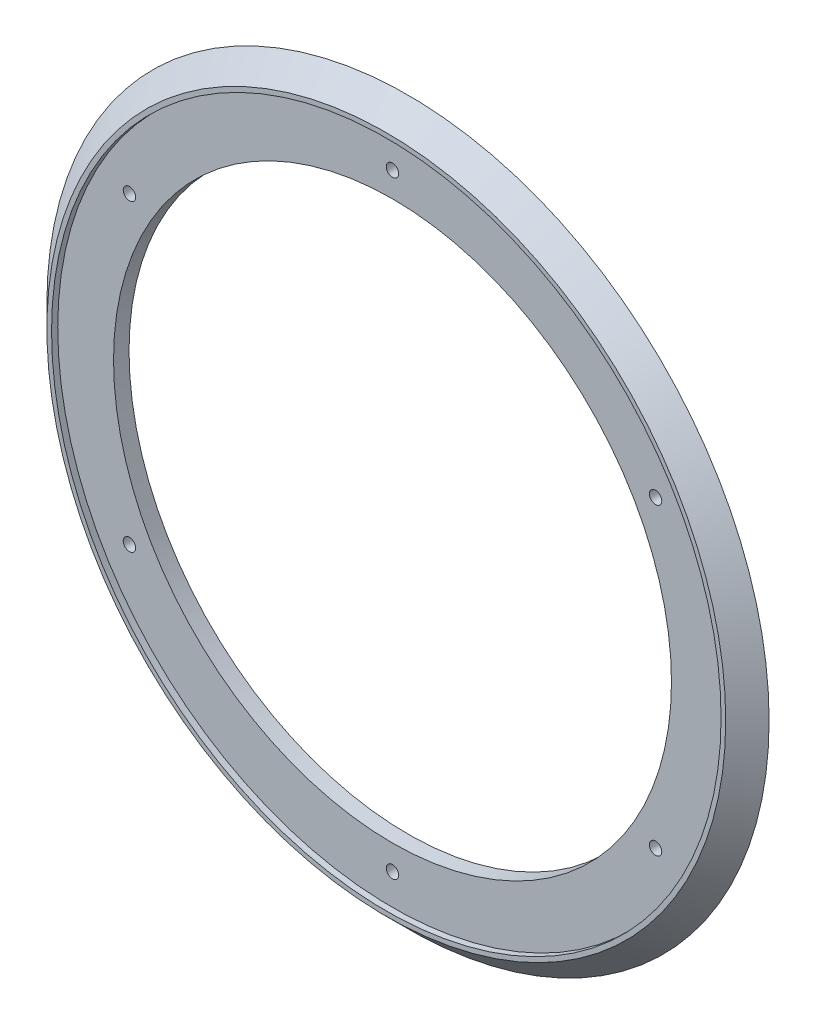
SolidWorks part; units mm, degrees
material "Gray Cast Iron (SN)"
ref_plane "Front Plane" through (0, 0, 0) normal (0, 0, 1) x (1, 0, 0)
ref_plane "Top Plane" through (0, 0, 0) normal (0, 1, 0) x (1, 0, 0)
ref_plane "Right Plane" through (0, 0, 0) normal (1, 0, 0) x (0, 0, -1)
sketch "Sketch1" plane through (0, 0, 0) normal (0, 0, 1) x (1, 0, 0)
  circle A0 centre (0, 0) radius 119.5
  dimension "D1" = 239
extrude "Boss-Extrude1" add sketch "Sketch1" along normal blind 7
chamfer "Chamfer2" distance 10 angle 45 1 edges at (119.5, 0, 7)
sketch "Sketch3" plane through (0, 0, 7) normal (0, 0, 1) x (1, 0, 0)
  circle A0 centre (0, 0) radius 108
  dimension "D1" = 216
extrude "Cut-Extrude1" cut sketch "Sketch3" against normal blind 2
sketch "Sketch4" plane through (0, 0, 0) normal (0, 0, -1) x (-1, 0, 0)
  circle A0 centre (0, 0) radius 90
  circle A1 centre (0, 0) radius 98 construction
  circle A2 centre (0, 98) radius 2
  circle A3 centre (84.8705, 49) radius 2
  circle A4 centre (84.8705, -49) radius 2
  circle A5 centre (0, -98) radius 2
  circle A6 centre (-84.8705, -49) radius 2
  circle A7 centre (-84.8705, 49) radius 2
  point P18 (0, 0)
  dimension "D1" = 180
  dimension "D2" = 196
  dimension "D3" = 4
  dimension "D4" = 6
extrude "Cut-Extrude2" cut sketch "Sketch4" against normal through all
